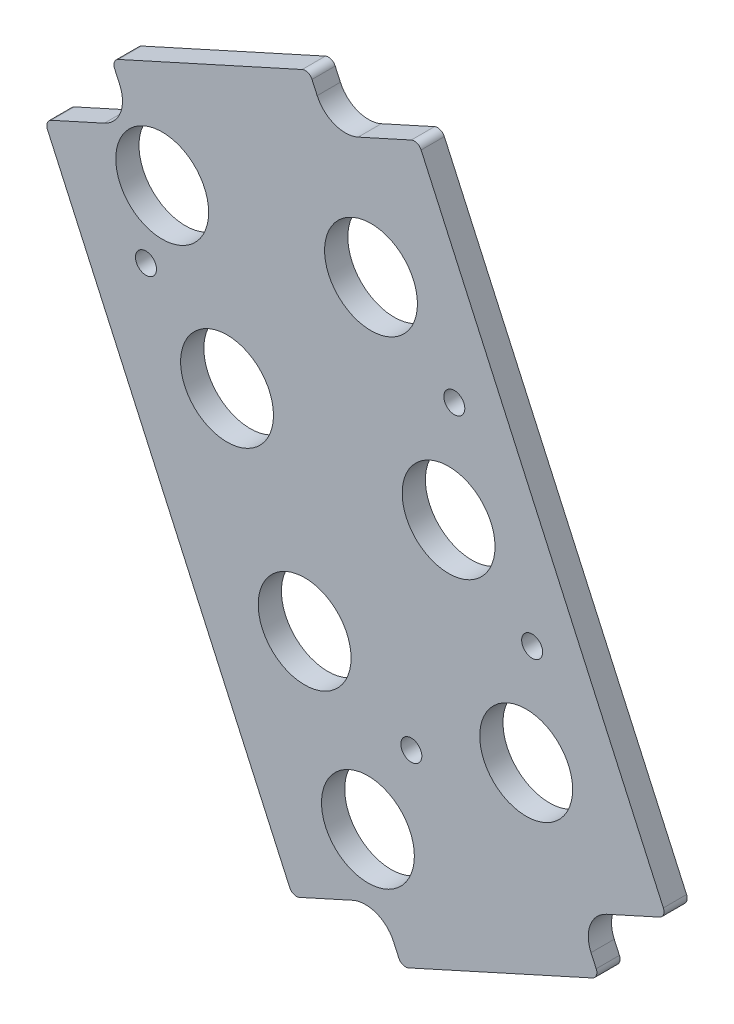
SolidWorks part; units mm, degrees
ref_plane "Front Plane" through (0, 0, 0) normal (0, 0, 1) x (1, 0, 0)
ref_plane "Top Plane" through (0, 0, 0) normal (0, 1, 0) x (1, 0, 0)
ref_plane "Right Plane" through (0, 0, 0) normal (1, 0, 0) x (0, 0, -1)
sketch "Sketch1" plane through (0, 0, 0) normal (0, 0, 1) x (1, 0, 0)
  line L12 (61.3283, -51.4439) -> (72.2336, -46.5094)
  line L13 (72.9939, -44.4927) -> (23.3092, 65.3127)
  line L14 (21.2925, 66.0729) -> (10.3871, 61.1385)
  line L15 (1.9841, 64.3061) -> (0.9239, 66.6491)
  line L16 (-1.0928, 67.4093) -> (-38.8131, 50.3417)
  line L17 (-39.5734, 48.325) -> (-38.5132, 45.9819)
  line L18 (-41.6808, 37.5789) -> (-52.5861, 32.6444)
  line L19 (-53.3463, 30.6277) -> (-3.6617, -79.1777)
  line L20 (-1.6449, -79.938) -> (9.2604, -75.0035)
  line L21 (17.6635, -78.1711) -> (18.7237, -80.5142)
  line L22 (20.7404, -81.2744) -> (58.4607, -64.2067)
  line L23 (59.2209, -62.19) -> (58.1607, -59.8469)
  line L24 (61.3283, -51.4439) -> (72.2336, -46.5094)
  line L25 (72.9939, -44.4927) -> (23.3092, 65.3127)
  line L26 (21.2925, 66.0729) -> (10.3871, 61.1385)
  line L27 (1.9841, 64.3061) -> (0.9239, 66.6491)
  line L28 (-1.0928, 67.4093) -> (-38.8131, 50.3417)
  line L29 (-39.5734, 48.325) -> (-38.5132, 45.9819)
  line L30 (-41.6808, 37.5789) -> (-52.5861, 32.6444)
  line L31 (-53.3463, 30.6277) -> (-3.6617, -79.1777)
  line L32 (-1.6449, -79.938) -> (9.2604, -75.0035)
  line L33 (17.6635, -78.1711) -> (18.7237, -80.5142)
  line L34 (20.7404, -81.2744) -> (58.4607, -64.2067)
  line L35 (59.2209, -62.19) -> (58.1607, -59.8469)
  arc A24 (61.3283, -51.4439) -> (58.1607, -59.8469) centre (63.946, -57.2292) ccw
  arc A25 (61.3283, -51.4439) -> (58.1607, -59.8469) centre (63.946, -57.2292) ccw
  arc A26 (72.2336, -46.5094) -> (72.9939, -44.4927) centre (71.6054, -45.121) ccw
  arc A27 (72.2336, -46.5094) -> (72.9939, -44.4927) centre (71.6054, -45.121) ccw
  arc A28 (23.3092, 65.3127) -> (21.2925, 66.0729) centre (21.9207, 64.6844) ccw
  arc A29 (23.3092, 65.3127) -> (21.2925, 66.0729) centre (21.9207, 64.6844) ccw
  arc A30 (1.9841, 64.3061) -> (10.3871, 61.1385) centre (7.7694, 66.9238) ccw
  arc A31 (1.9841, 64.3061) -> (10.3871, 61.1385) centre (7.7694, 66.9238) ccw
  arc A32 (0.9239, 66.6491) -> (-1.0928, 67.4093) centre (-0.4646, 66.0209) ccw
  arc A33 (0.9239, 66.6491) -> (-1.0928, 67.4093) centre (-0.4646, 66.0209) ccw
  arc A34 (-38.8131, 50.3417) -> (-39.5734, 48.325) centre (-38.1849, 48.9532) ccw
  arc A35 (-38.8131, 50.3417) -> (-39.5734, 48.325) centre (-38.1849, 48.9532) ccw
  arc A9432 (-41.6808, 37.5789) -> (-38.5132, 45.9819) centre (-44.2985, 43.3642) ccw
  arc A9433 (-41.6808, 37.5789) -> (-38.5132, 45.9819) centre (-44.2985, 43.3642) ccw
  arc A9434 (-52.5861, 32.6444) -> (-53.3463, 30.6277) centre (-51.9578, 31.2559) ccw
  arc A9435 (-52.5861, 32.6444) -> (-53.3463, 30.6277) centre (-51.9578, 31.2559) ccw
  arc A9436 (-3.6617, -79.1777) -> (-1.6449, -79.938) centre (-2.2732, -78.5495) ccw
  arc A9437 (-3.6617, -79.1777) -> (-1.6449, -79.938) centre (-2.2732, -78.5495) ccw
  arc A9438 (17.6635, -78.1711) -> (9.2604, -75.0035) centre (11.8781, -80.7888) ccw
  arc A9439 (17.6635, -78.1711) -> (9.2604, -75.0035) centre (11.8781, -80.7888) ccw
  arc A9440 (18.7237, -80.5142) -> (20.7404, -81.2744) centre (20.1121, -79.8859) ccw
  arc A9441 (18.7237, -80.5142) -> (20.7404, -81.2744) centre (20.1121, -79.8859) ccw
  arc A9442 (58.4607, -64.2067) -> (59.2209, -62.19) centre (57.8324, -62.8183) ccw
  arc A9443 (58.4607, -64.2067) -> (59.2209, -62.19) centre (57.8324, -62.8183) ccw
  dimension "D1" = 0
extrude "Boss-Extrude1" add sketch "Sketch1" along normal blind 4.7625
hole_wizard "#6 Clearance Hole1" positions "Sketch5" profile "Sketch4" hole size "#6" standard "ANSI Inch" end condition through all
sketch "Sketch5" plane through (0, 0, 4.7625) normal (0, 0, 1) x (1, 0, 0)
  point P0 (30.1147, 23.8551)
  point P3 (46.0829, -11.4354)
  point P6 (-33.1289, 16.9844)
  point P9 (21.2985, -42.3046)
sketch "Sketch4" plane through (30.1147, 23.8551, 4.7625) normal (1, 0, 0) x (0, -1, 0)
  line L0 (0, 0) -> (0, 4.7625)
  line L1 (0, 4.7625) -> (2.1526, 4.7625)
  line L2 (2.1526, 4.7625) -> (2.1526, 0)
  line L5 (2.1526, 0) -> (0, 0)
  line L11 (0, -6.35) -> (0, 107.95) construction
  dimension "Thru Hole Dia." = 4.3053
  dimension "Thru Hole Depth" = 4.7625
sketch "Sketch6" plane through (0, 0, 4.7625) normal (0, 0, 1) x (1, 0, 0)
  circle A5 centre (13.027, 37.5902) radius 9.525
  circle A6 centre (28.9428, 2.4154) radius 9.525
  circle A7 centre (44.8587, -32.7593) radius 9.525
  circle A8 centre (-16.504, 3.0399) radius 9.525
  circle A9 centre (-0.5881, -32.1349) radius 9.525
  circle A10 centre (-29.8021, 32.4293) radius 9.525
  circle A11 centre (12.3958, -60.8301) radius 9.525
  dimension "D1" = 19.05
extrude "Cut-Extrude1" cut sketch "Sketch6" against normal through all
